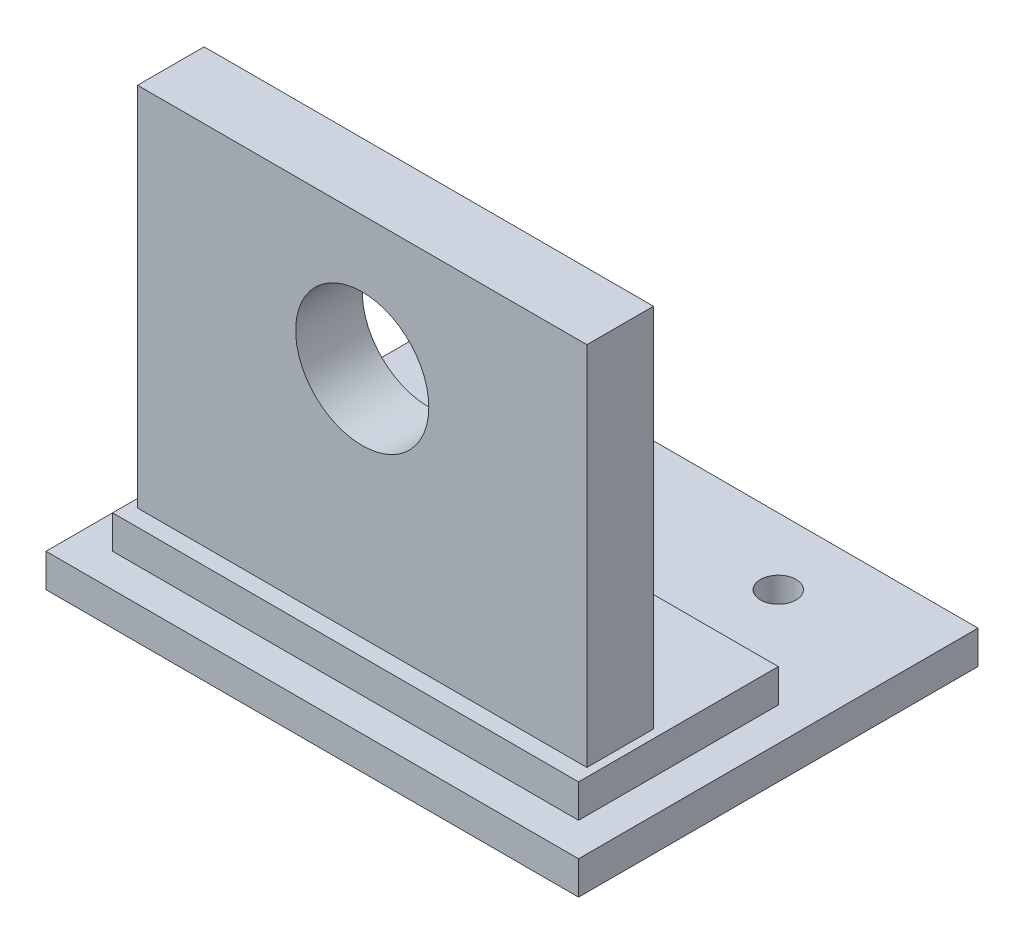
SolidWorks part; units mm, degrees
material "6061 Alloy"
ref_plane "Front Plane" through (0, 0, 0) normal (0, 0, 1) x (1, 0, 0)
ref_plane "Top Plane" through (0, 0, 0) normal (0, 1, 0) x (1, 0, 0)
ref_plane "Right Plane" through (0, 0, 0) normal (1, 0, 0) x (0, 0, -1)
sketch "Sketch2" plane through (0, 0, 0) normal (0, 1, 0) x (1, 0, 0)
  line L1 (-25.4, -12.7) -> (25.4, -12.7)
  line L2 (-25.4, -12.7) -> (-25.4, 12.7)
  line L4 (25.4, -12.7) -> (25.4, 12.7)
  line L5 (-25.4, -12.7) -> (25.4, 12.7) construction
  line L6 (-25.4, 12.7) -> (25.4, -12.7) construction
  line L8 (-25.4, 12.7) -> (-25.4, 25.4)
  line L9 (-25.4, 25.4) -> (25.4, 25.4)
  line L10 (25.4, 12.7) -> (25.4, 25.4)
  line L11 (0, 0) -> (0, 25.4) construction
  line L12 (-12.7, 19.05) -> (12.7, 19.05) construction
  point P0 (0, 0)
  point P6 (0, 19.05)
  point P14 (-12.7, 19.05)
  point P15 (12.7, 19.05)
  dimension "D1" = 50.8
  dimension "D2" = 25.4
  dimension "D3" = 12.7
  dimension "D4" = 25.4
  dimension "D5" = 6.35
extrude "Boss-Extrude1" add sketch "Sketch2" along normal blind 3.175
sketch "Sketch3" plane through (0, 3.175, 0) normal (0, 1, 0) x (1, 0, 0)
  line L0 (-25.4, -12.7) -> (25.4, -12.7) construction
  line L1 (-22.225, -9.525) -> (22.225, -9.525)
  line L2 (-22.225, -9.525) -> (-22.225, 9.525)
  line L3 (-22.225, 9.525) -> (22.225, 9.525)
  line L4 (22.225, -9.525) -> (22.225, 9.525)
  line L5 (-22.225, -9.525) -> (22.225, 9.525) construction
  line L6 (-22.225, 9.525) -> (22.225, -9.525) construction
  line L7 (-25.4, 25.4) -> (-25.4, -12.7) construction
  point P0 (0, 0)
  dimension "D2" = 3.175
  dimension "D1" = 3.175
extrude "Boss-Extrude2" add sketch "Sketch3" along normal blind 3.175
sketch "Sketch4" plane through (0, 6.35, 0) normal (0, 1, 0) x (1, 0, 0)
  line L0 (-22.225, -9.525) -> (22.225, -9.525) construction
  line L1 (-21.4313, -7.9375) -> (21.4313, -7.9375)
  line L2 (-21.4313, -7.9375) -> (-21.4313, -1.5875)
  line L3 (-21.4313, -1.5875) -> (21.4313, -1.5875)
  line L4 (21.4313, -7.9375) -> (21.4313, -1.5875)
  line L5 (-22.225, 9.525) -> (-22.225, -9.525) construction
  line L6 (0, 0) -> (0, -5.569) construction
  dimension "D1" = 1.5875
  dimension "D2" = 0.7937
  dimension "D3" = 6.35
extrude "Boss-Extrude3" add sketch "Sketch4" along normal blind 34.925
sketch "Sketch5" plane through (0, 0, 7.9375) normal (0, 0, 1) x (1, 0, 0)
  line L0 (0, 28.575) -> (0, 0) construction
  line L1 (-25.4, 3.175) -> (25.4, 3.175) construction
  circle A0 centre (0, 28.575) radius 6.35
  dimension "D2" = 12.7
  dimension "D1" = 25.4
extrude "Cut-Extrude1" cut sketch "Sketch5" against normal blind 34.925
hole_wizard "M3 Clearance Hole1" positions "3DSketch1" profile "Sketch6" hole size "M3" standard "ANSI Metric" end condition through all
sketch3d "3DSketch1"
  point P0 (-12.7, 0, -19.05)
  point P3 (12.7, 0, -19.05)
sketch "Sketch6" plane through (-12.7, 0, -19.05) normal (1, 0, 0) x (0, 0, -1)
  line L0 (0, 0) -> (0, 41.275)
  line L1 (0, 41.275) -> (1.7, 41.275)
  line L2 (1.7, 41.275) -> (1.7, 0)
  line L5 (1.7, 0) -> (0, 0)
  line L11 (0, -6.35) -> (0, 107.95) construction
  dimension "Thru Hole Dia." = 3.4
  dimension "Thru Hole Depth" = 41.275
equation "\"D2@Sketch3\"=\"D1@Sketch3\""
